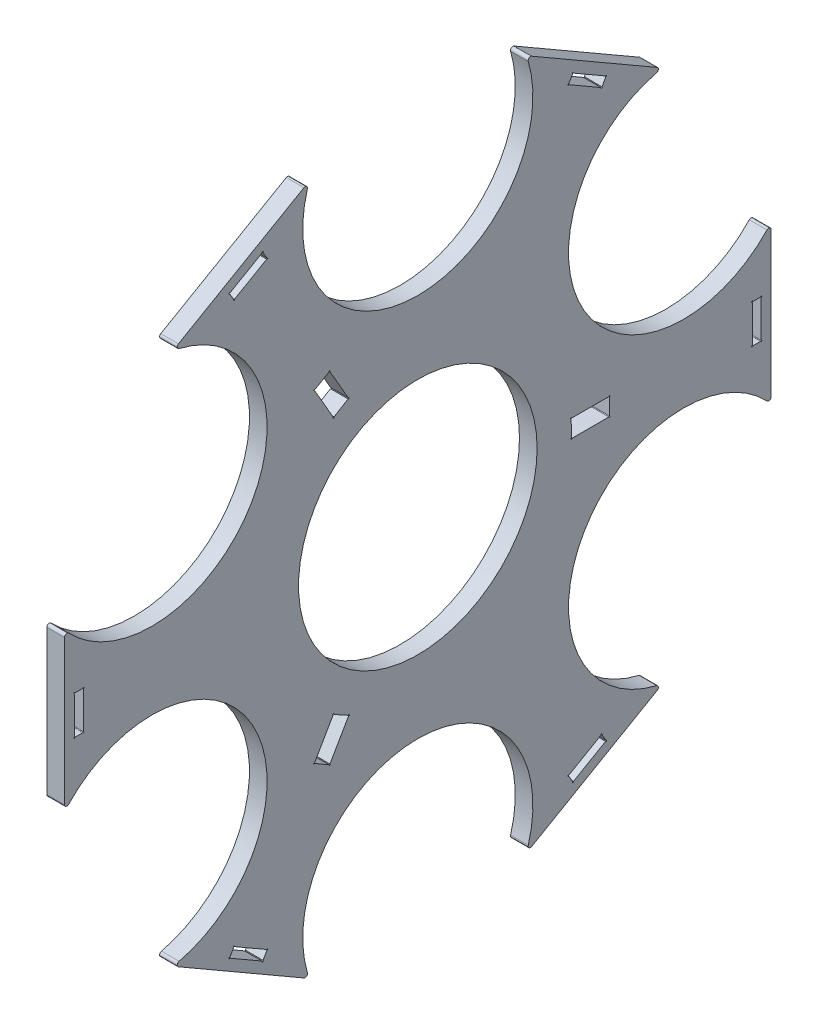
SolidWorks part; units mm, degrees
ref_plane "Front Plane" through (0, 0, 0) normal (0, 0, 1) x (1, 0, 0)
ref_plane "Top Plane" through (0, 0, 0) normal (0, 1, 0) x (1, 0, 0)
ref_plane "Right Plane" through (0, 0, 0) normal (1, 0, 0) x (0, 0, -1)
sketch "Sketch2" plane through (0, 0, 0) normal (1, 0, 0) x (0, 0, -1)
  line L0 (35.921, 114.3) -> (-35.921, 114.3) construction
  line L1 (81.0262, 88.2585) -> (35.921, 114.3)
  line L2 (116.9472, -26.0415) -> (116.9472, 26.0415)
  line L3 (35.921, -114.3) -> (81.0262, -88.2585)
  line L4 (-81.0262, -88.2585) -> (-35.921, -114.3)
  line L5 (-116.9472, 26.0415) -> (-116.9472, -26.0415)
  line L6 (-35.921, 114.3) -> (-81.0262, 88.2585)
  circle A0 centre (0, 0) radius 101.6 construction
  arc A1 (-35.921, 114.3) -> (35.921, 114.3) centre (0, 101.6) ccw
  arc A2 (81.0262, 88.2585) -> (116.9472, 26.0415) centre (87.9882, 50.8) ccw
  arc A3 (116.9472, -26.0415) -> (81.0262, -88.2585) centre (87.9882, -50.8) ccw
  arc A4 (35.921, -114.3) -> (-35.921, -114.3) centre (0, -101.6) ccw
  arc A5 (-81.0262, -88.2585) -> (-116.9472, -26.0415) centre (-87.9882, -50.8) ccw
  arc A6 (-116.9472, 26.0415) -> (-81.0262, 88.2585) centre (-87.9882, 50.8) ccw
  circle A7 centre (0, 0) radius 39.4875
  point P23 (0, 0)
  point P34 (0, 0)
  dimension "D1" = 203.2
  dimension "D2" = 114.3
  dimension "D3" = 76.2
  dimension "D6" = 78.9749
  dimension "D4" = 6
  dimension "D5" = 6
extrude "Boss-Extrude1" add sketch "Sketch2" along normal blind 5.842 contours A6 L5 A5 L4 A4 L3 A3 L2 A2 L1 A1 L6 region at (0, 30.1147, -52.1602)
fillet "Fillet1" radius 0.7937 12 edges at (2.921, -114.3, 35.921) (2.921, -114.3, -35.921) (2.921, -88.2585, -81.0262) (2.921, -26.0415, -116.9472) (2.921, 88.2585, -81.0262) (2.921, 26.0415, -116.9472) (2.921, -88.2585, 81.0262) (2.921, -26.0415, 116.9472) (2.921, 26.0415, 116.9472) (2.921, 88.2585, 81.0262) (2.921, 114.3, -35.921) (2.921, 114.3, 35.921)
sketch "Sketch6" plane through (5.842, 0, 0) normal (1, 0, 0) x (0, 0, -1)
  line L0 (0, 0) -> (-58.4736, 101.2793) construction
  line L1 (-37.7084, 113.2681) -> (-79.2388, 89.2905) construction
  line L2 (-28.575, 49.4934) -> (-22.225, 38.4948) construction
  line L3 (-23.0045, 45.6869) -> (-29.0967, 56.239)
  line L4 (-28.0045, 42.6631) -> (-34.156, 53.318)
  line L5 (-34.0834, 53.589) -> (-29.3678, 56.3116)
  line L6 (-27.7354, 42.594) -> (-23.075, 45.4123)
  line L8 (2.5297, 1.4605) -> (-55.9439, 102.7398) construction
  line L9 (-2.5297, -1.4605) -> (-61.0033, 99.8188) construction
  arc A0 (-29.0967, 56.239) -> (-29.3678, 56.3116) centre (-29.1959, 56.4108) ccw
  arc A1 (-23.075, 45.4123) -> (-23.0045, 45.6869) centre (-22.9052, 45.515) ccw
  arc A2 (-28.0045, 42.6631) -> (-27.7354, 42.594) centre (-27.9052, 42.4913) ccw
  arc A3 (-34.0834, 53.589) -> (-34.156, 53.318) centre (-34.2552, 53.4898) ccw
  point P8 (-25.4, 43.9941)
  point P12 (-25.4052, 44.0032)
  point P28 (0, 0)
  dimension "D8" = 0.3969
  dimension "D9" = 0.3969
  dimension "D10" = 0.3969
  dimension "D11" = 0.3969
  dimension "D1" = 12.7
  dimension "D2" = 12.5814
  dimension "D5" = 12.7
  dimension "D6" = 50.8
  dimension "D3" = 2.921
  dimension "D4" = 2.921
extrude "Cut-Extrude2" cut sketch "Sketch6" against normal through all
pattern_circular "CirPattern2" count 3 every 120 about axis through (5.842, 0, 0) along (-1, 0, 0) of "Cut-Extrude2"
sketch "Sketch11" plane through (0, 0, 0) normal (-1, 0, 0) x (0, 0, 1)
  line L0 (0, 0) -> (-58.4736, 101.2793) construction
  line L1 (-79.2388, 89.2905) -> (-37.7084, 113.2681) construction
  line L2 (-25.6393, 114.7369) -> (-86.5454, 79.5727) construction
  line L3 (-50.0212, 98.9424) -> (-60.676, 92.7908)
  line L4 (-49.9486, 99.2135) -> (-51.2376, 101.4462)
  line L5 (-60.9471, 92.8635) -> (-62.2362, 95.0962)
  line L6 (-51.5087, 101.5188) -> (-62.1635, 95.3672)
  line L7 (-49.8493, 99.0416) -> (-62.3354, 95.268) construction
  line L8 (-60.8479, 92.6916) -> (-51.3368, 101.618) construction
  line L9 (60.676, 92.7908) -> (50.0212, 98.9424)
  line L10 (60.9471, 92.8635) -> (62.2362, 95.0962)
  line L11 (49.9486, 99.2135) -> (51.2376, 101.4462)
  line L12 (62.1635, 95.3672) -> (51.5087, 101.5188)
  line L13 (0, 0) -> (58.4736, 101.2793) construction
  line L14 (86.5454, 79.5727) -> (25.6393, 114.7369) construction
  line L15 (60.8479, 92.6916) -> (51.3368, 101.618) construction
  line L16 (49.8493, 99.0416) -> (62.3354, 95.268) construction
  line L17 (110.6972, -6.1516) -> (110.6972, 6.1516)
  line L18 (110.8957, -6.35) -> (113.4738, -6.35)
  line L19 (110.8957, 6.35) -> (113.4738, 6.35)
  line L20 (113.6722, -6.1516) -> (113.6722, 6.1516)
  line L21 (0, 0) -> (116.9472, 0) construction
  line L22 (112.1847, -35.1642) -> (112.1847, 35.1642) construction
  line L23 (110.6972, -6.35) -> (113.6722, 6.35) construction
  line L24 (110.6972, 6.35) -> (113.6722, -6.35) construction
  line L25 (50.0212, -98.9424) -> (60.676, -92.7908)
  line L26 (49.9486, -99.2135) -> (51.2376, -101.4462)
  line L27 (60.9471, -92.8635) -> (62.2362, -95.0962)
  line L28 (51.5087, -101.5188) -> (62.1635, -95.3672)
  line L29 (0, 0) -> (58.4736, -101.2793) construction
  line L30 (25.6393, -114.7369) -> (86.5454, -79.5727) construction
  line L31 (49.8493, -99.0416) -> (62.3354, -95.268) construction
  line L32 (60.8479, -92.6916) -> (51.3368, -101.618) construction
  line L33 (-60.676, -92.7908) -> (-50.0212, -98.9424)
  line L34 (-60.9471, -92.8635) -> (-62.2362, -95.0962)
  line L35 (-49.9486, -99.2135) -> (-51.2376, -101.4462)
  line L36 (-62.1635, -95.3672) -> (-51.5087, -101.5188)
  line L37 (0, 0) -> (-58.4736, -101.2793) construction
  line L38 (-86.5454, -79.5727) -> (-25.6393, -114.7369) construction
  line L39 (-60.8479, -92.6916) -> (-51.3368, -101.618) construction
  line L40 (-49.8493, -99.0416) -> (-62.3354, -95.268) construction
  line L41 (-110.6972, 6.1516) -> (-110.6972, -6.1516)
  line L42 (-110.8957, 6.35) -> (-113.4738, 6.35)
  line L43 (-110.8957, -6.35) -> (-113.4738, -6.35)
  line L44 (-113.6722, 6.1516) -> (-113.6722, -6.1516)
  line L45 (0, 0) -> (-116.9472, 0) construction
  line L46 (-112.1847, 35.1642) -> (-112.1847, -35.1642) construction
  line L47 (-110.6972, 6.35) -> (-113.6722, -6.35) construction
  line L48 (-110.6972, -6.35) -> (-113.6722, 6.35) construction
  arc A0 (-62.1635, 95.3672) -> (-62.2362, 95.0962) centre (-62.3354, 95.268) ccw
  arc A1 (-51.2376, 101.4462) -> (-51.5087, 101.5188) centre (-51.3368, 101.618) ccw
  arc A2 (-50.0212, 98.9424) -> (-49.9486, 99.2135) centre (-49.8493, 99.0416) ccw
  arc A3 (-60.9471, 92.8635) -> (-60.676, 92.7908) centre (-60.8479, 92.6916) ccw
  arc A4 (51.5087, 101.5188) -> (51.2376, 101.4462) centre (51.3368, 101.618) ccw
  arc A5 (62.2362, 95.0962) -> (62.1635, 95.3672) centre (62.3354, 95.268) ccw
  arc A6 (60.676, 92.7908) -> (60.9471, 92.8635) centre (60.8479, 92.6916) ccw
  arc A7 (49.9486, 99.2135) -> (50.0212, 98.9424) centre (49.8493, 99.0416) ccw
  arc A8 (113.6722, 6.1516) -> (113.4738, 6.35) centre (113.6722, 6.35) ccw
  arc A9 (113.4738, -6.35) -> (113.6722, -6.1516) centre (113.6722, -6.35) ccw
  arc A10 (110.6972, -6.1516) -> (110.8957, -6.35) centre (110.6972, -6.35) ccw
  arc A11 (110.8957, 6.35) -> (110.6972, 6.1516) centre (110.6972, 6.35) ccw
  arc A12 (62.1635, -95.3672) -> (62.2362, -95.0962) centre (62.3354, -95.268) ccw
  arc A13 (51.2376, -101.4462) -> (51.5087, -101.5188) centre (51.3368, -101.618) ccw
  arc A14 (50.0212, -98.9424) -> (49.9486, -99.2135) centre (49.8493, -99.0416) ccw
  arc A15 (60.9471, -92.8635) -> (60.676, -92.7908) centre (60.8479, -92.6916) ccw
  arc A16 (-51.5087, -101.5188) -> (-51.2376, -101.4462) centre (-51.3368, -101.618) ccw
  arc A17 (-62.2362, -95.0962) -> (-62.1635, -95.3672) centre (-62.3354, -95.268) ccw
  arc A18 (-60.676, -92.7908) -> (-60.9471, -92.8635) centre (-60.8479, -92.6916) ccw
  arc A19 (-49.9486, -99.2135) -> (-50.0212, -98.9424) centre (-49.8493, -99.0416) ccw
  arc A20 (-113.6722, -6.1516) -> (-113.4738, -6.35) centre (-113.6722, -6.35) ccw
  arc A21 (-113.4738, 6.35) -> (-113.6722, 6.1516) centre (-113.6722, 6.35) ccw
  arc A22 (-110.6972, 6.1516) -> (-110.8957, 6.35) centre (-110.6972, 6.35) ccw
  arc A23 (-110.8957, -6.35) -> (-110.6972, -6.1516) centre (-110.6972, -6.35) ccw
  point P8 (-56.0924, 97.1548)
  point P9 (-56.0924, 97.1548)
  point P27 (56.0924, 97.1548)
  point P28 (56.0924, 97.1548)
  point P44 (112.1847, 0)
  point P45 (112.1847, 0)
  point P61 (56.0924, -97.1548)
  point P62 (56.0924, -97.1548)
  point P78 (-56.0924, -97.1548)
  point P79 (-56.0924, -97.1548)
  point P95 (-112.1847, 0)
  point P96 (-112.1847, 0)
  point P108 (0, 0)
  dimension "D4" = 0.3969
  dimension "D5" = 0.3969
  dimension "D6" = 0.3969
  dimension "D7" = 0.3969
  dimension "D1" = 4.7625
  dimension "D2" = 2.975
  dimension "D3" = 12.7
  dimension "D8" = 6
extrude "Cut-Extrude5" cut sketch "Sketch11" against normal through all
